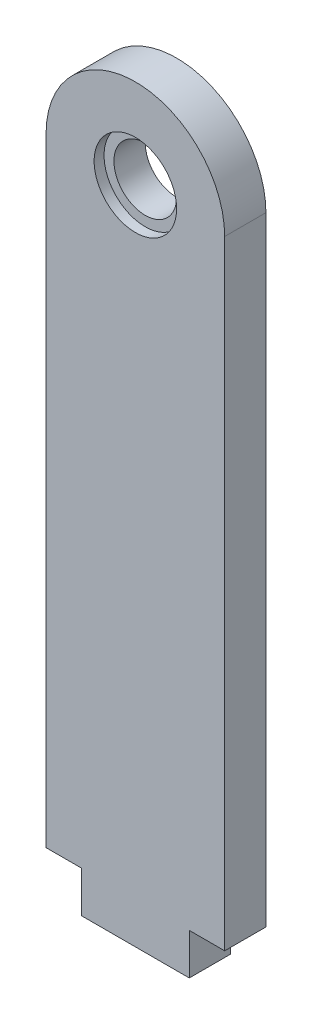
SolidWorks part; units mm, degrees
ref_plane "Front Plane" through (0, 0, 0) normal (0, 0, 1) x (1, 0, 0)
ref_plane "Top Plane" through (0, 0, 0) normal (0, 1, 0) x (1, 0, 0)
ref_plane "Right Plane" through (0, 0, 0) normal (1, 0, 0) x (0, 0, -1)
sketch "Sketch1" plane through (0, 0, 0) normal (0, 0, 1) x (1, 0, 0)
  line L1 (0, 0) -> (27.5, 0)
  line L2 (0, 0) -> (0, 95.25)
  line L3 (0, 95.25) -> (27.5, 95.25)
  line L4 (27.5, 0) -> (27.5, 95.25)
  line L5 (5.4495, 0) -> (22.0505, 0)
  line L6 (5.4495, 0) -> (5.4495, -6.35)
  line L7 (5.4495, -6.35) -> (22.0505, -6.35)
  line L8 (22.0505, 0) -> (22.0505, -6.35)
  arc A0 (0, 95.25) -> (27.5, 95.25) centre (13.75, 95.25) cw
  circle A1 centre (13.75, 95.25) radius 4.826
  circle A2 centre (13.75, 95.25) radius 6.35
  point P12 (13.75, 0)
  point P13 (13.75, 0)
  point P14 (0, 0)
  point P15 (0, 0)
  dimension "D1" = 9.652
  dimension "D2" = 12.7
  dimension "D3" = 6.35
  dimension "D4" = 101.6
  dimension "D5" = 27.5
extrude "Boss-Extrude1" add sketch "Sketch1" along normal blind 6.35 contours A2 L3 L2 L1 L4 | L3 A2 A1 | L3 A2 A1 | A2 L3 A0 | L8 L1 L6 L7 region at (13.75, 46.5116, 0) region at (13.75, -3.175, 0) region at (13.75, 101.9371, 0) region at (13.75, 101.458, 0) region at (8.162, 95.108, 0)
sketch "Sketch2" plane through (0, 0, 6.35) normal (0, 0, 1) x (1, 0, 0)
  line L7 (0, 95.25) -> (0, 0)
  line L8 (0, 0) -> (5.4495, 0)
  line L9 (5.4495, 0) -> (5.4495, -6.35)
  line L10 (5.4495, -6.35) -> (22.0505, -6.35)
  line L11 (22.0505, -6.35) -> (22.0505, 0)
  line L12 (22.0505, 0) -> (27.5, 0)
  line L13 (27.5, 0) -> (27.5, 95.25)
  line L14 (0, 95.25) -> (0, 0)
  line L15 (0, 0) -> (5.4495, 0)
  line L16 (5.4495, 0) -> (5.4495, -6.35)
  line L17 (5.4495, -6.35) -> (22.0505, -6.35)
  line L18 (22.0505, -6.35) -> (22.0505, 0)
  line L19 (22.0505, 0) -> (27.5, 0)
  line L20 (27.5, 0) -> (27.5, 95.25)
  circle A0 centre (13.75, 95.25) radius 4.826 construction
  arc A1 (27.5, 95.25) -> (0, 95.25) centre (13.75, 95.25) ccw
  arc A2 (27.5, 95.25) -> (0, 95.25) centre (13.75, 95.25) ccw
  circle A3 centre (13.75, 95.25) radius 4.826
  circle A4 centre (13.75, 95.25) radius 6.35
  circle M9 centre (13.75, 95.25) radius 4.826
  dimension "D2" = 12.7
  dimension "D1" = 0
extrude "Cut-Extrude1" cut sketch "Sketch2" against normal blind 1.524 contours A4 M9 region at (7.5796, 95.25, 6.35)
